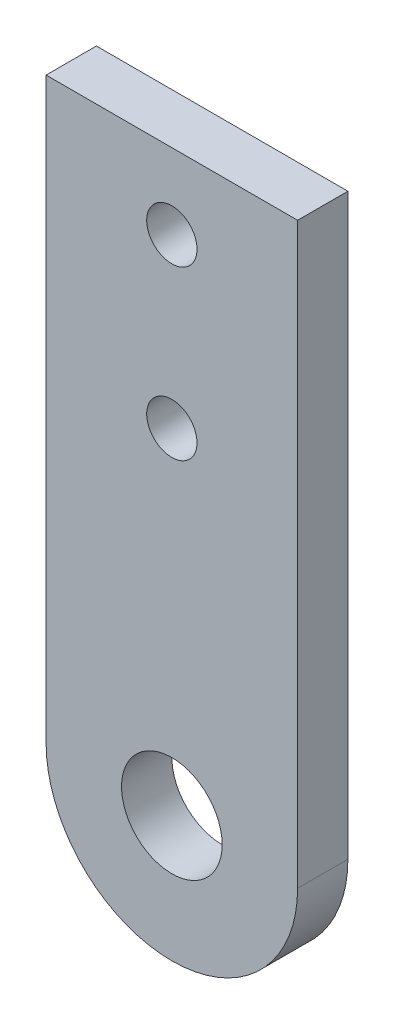
SolidWorks part; units mm, degrees
material "Thornel Mat VMA"
ref_plane "前视基准面" through (0, 0, 0) normal (0, 0, 1) x (1, 0, 0)
ref_plane "上视基准面" through (0, 0, 0) normal (0, 1, 0) x (1, 0, 0)
ref_plane "右视基准面" through (0, 0, 0) normal (1, 0, 0) x (0, 0, -1)
sketch "草图1" plane through (0, 0, 0) normal (0, 0, 1) x (1, 0, 0)
  line L1 (-7.5, 21) -> (7.5, 21)
  line L2 (-7.5, 21) -> (-7.5, -21)
  line L3 (-7.5, -21) -> (7.5, -21)
  line L4 (7.5, 21) -> (7.5, -21)
  line L5 (-7.5, 21) -> (7.5, -21) construction
  line L6 (-7.5, -21) -> (7.5, 21) construction
  point P0 (0, 0)
  dimension "D1" = 15
  dimension "D2" = 42
extrude "凸台-拉伸1" add sketch "草图1" along normal blind 3
sketch "草图3" plane through (0, 0, 3) normal (0, 0, 1) x (1, 0, 0)
  line L0 (0, 21) -> (0, -21) construction
  line L1 (7.5, 21) -> (-7.5, 21) construction
  line L2 (-7.5, -21) -> (7.5, -21) construction
  circle A0 centre (0, 16.5) radius 1.5
  circle A1 centre (0, 6.5) radius 1.5
  circle A3 centre (0, -13.5) radius 3
  dimension "D1" = 3
  dimension "D2" = 6
  dimension "D3" = 20
  dimension "D4" = 10
  dimension "D6" = 7.5
extrude "切除-拉伸1" cut sketch "草图3" against normal through all
fillet "圆角1" radius 7.5 2 edges at (-7.5, -21, 1.5) (7.5, -21, 1.5)
